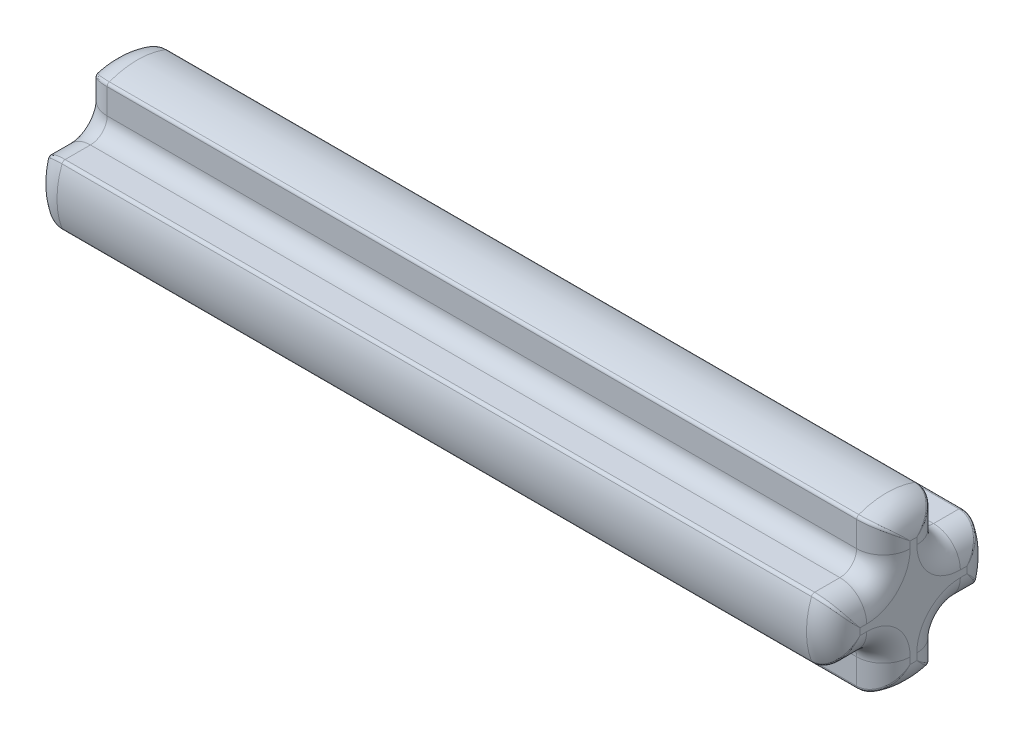
SolidWorks part; units mm, degrees
material "PET"
ref_plane "Alzado" through (0, 0, 0) normal (0, 0, 1) x (1, 0, 0)
ref_plane "Planta" through (0, 0, 0) normal (0, 1, 0) x (1, 0, 0)
ref_plane "Vista lateral" through (0, 0, 0) normal (1, 0, 0) x (0, 0, -1)
sketch "Croquis1" plane through (0, 0, 0) normal (1, 0, 0) x (0, 0, -1)
  line B0 (-1.4, 0.9) -> (-2.2249, 0.9)
  line B1 (0.9, -2.2249) -> (0.9, -1.4)
  line B2 (-0.9, -2.2249) -> (-0.9, -1.4)
  line B3 (2.2249, 0.9) -> (1.4, 0.9)
  line B4 (2.2249, -0.9) -> (1.4, -0.9)
  line B5 (-0.9, 1.4) -> (-0.9, 2.2249)
  line B6 (0.9, 1.4) -> (0.9, 2.2249)
  line B7 (-1.4, -0.9) -> (-2.2249, -0.9)
  arc B8 (-2.2249, 0.9) -> (-2.2249, -0.9) centre (0, 0) ccw
  arc B9 (-1.4, -0.9) -> (-0.9, -1.4) centre (-1.4, -1.4) cw
  arc B10 (0.9, -1.4) -> (1.4, -0.9) centre (1.4, -1.4) cw
  arc B11 (1.4, 0.9) -> (0.9, 1.4) centre (1.4, 1.4) cw
  arc B12 (-0.9, 1.4) -> (-1.4, 0.9) centre (-1.4, 1.4) cw
  arc B13 (0.9, 2.2249) -> (-0.9, 2.2249) centre (0, 0) ccw
  arc B14 (2.2249, -0.9) -> (2.2249, 0.9) centre (0, 0) ccw
  arc B15 (-0.9, -2.2249) -> (0.9, -2.2249) centre (0, 0) ccw
sketch_block_instance "Axle Section Block-1"
sketch_block "Axle Section Block" parameters "D1"=4.8, "D3"=0.5, "D2"=1.8
extrude "Saliente-Extruir1" add sketch "Croquis1" along normal blind 24
fillet "Redondeo1" radius 0.1 8 edges at (12, -2.2249, -0.9) (12, -0.9, -2.2249) (12, 0.9, -2.2249) (12, 2.2249, -0.9) (12, 2.2249, 0.9) (12, -2.2249, 0.9) (12, -0.9, 2.2249) (12, 0.9, 2.2249)
fillet "Redondeo2" radius 0.8 48 edges at (0, 1.7782, 0.9) (0, 1.0464, 1.0464) (0, 0.9, 1.7782) (0, 0, 2.4) (0, -0.9, 1.7782) (0, -1.0464, 1.0464) (0, -1.7782, 0.9) (0, -2.4, 0) (0, -1.7782, -0.9) (0, -1.0464, -1.0464) (0, -0.9, -1.7782) (0, 0, -2.4) (0, 0.9, -1.7782) (0, 1.0464, -1.0464) (0, 1.7782, -0.9) (0, 2.4, 0) (24, 1.7782, -0.9) (24, 1.0464, -1.0464) (24, 0.9, -1.7782) (24, 0, -2.4) (24, -0.9, -1.7782) (24, -1.0464, -1.0464) (24, -1.7782, -0.9) (24, -2.4, 0) (24, -1.7782, 0.9) (24, -1.0464, 1.0464) (24, -0.9, 1.7782) (24, 0, 2.4) (24, 0.9, 1.7782) (24, 1.0464, 1.0464) (24, 1.7782, 0.9) (24, 2.4, 0) (0, -0.8821, -2.2135) (0, 0.8821, -2.2135) (0, 2.2135, -0.8821) (0, 2.2135, 0.8821) (0, 0.8821, 2.2135) (0, -0.8821, 2.2135) (0, -2.2135, 0.8821) (0, -2.2135, -0.8821) (24, -2.2135, 0.8821) (24, -0.8821, 2.2135) (24, 0.8821, 2.2135) (24, 2.2135, 0.8821) (24, 2.2135, -0.8821) (24, 0.8821, -2.2135) (24, -0.8821, -2.2135) (24, -2.2135, -0.8821)
